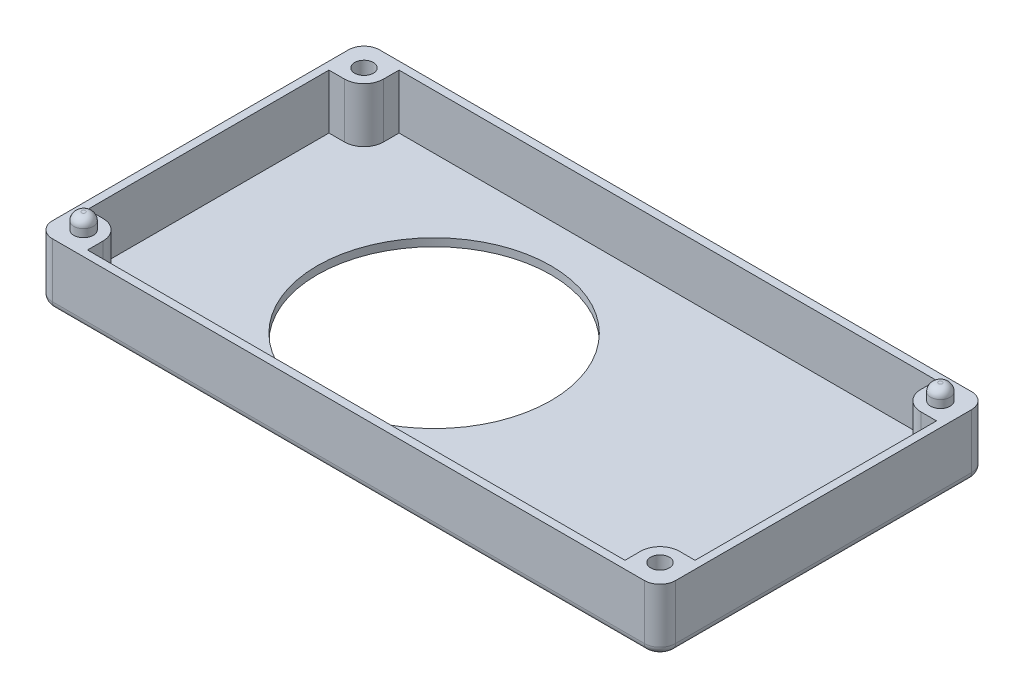
SolidWorks part; units mm, degrees
ref_plane "Front Plane" through (0, 0, 0) normal (0, 0, 1) x (1, 0, 0)
ref_plane "Top Plane" through (0, 0, 0) normal (0, 1, 0) x (1, 0, 0)
ref_plane "Right Plane" through (0, 0, 0) normal (1, 0, 0) x (0, 0, -1)
sketch "Sketch1" plane through (0, 0, 0) normal (0, 1, 0) x (1, 0, 0)
  line L1 (-40, -21) -> (40, -21)
  line L2 (-40, -21) -> (-40, 21)
  line L3 (-40, 21) -> (40, 21)
  line L4 (40, -21) -> (40, 21)
  line L5 (-40, -21) -> (40, 21) construction
  line L6 (-40, 21) -> (40, -21) construction
  point P0 (0, 0)
  dimension "D1" = 42
  dimension "D2" = 80
extrude "Boss-Extrude1" add sketch "Sketch1" along normal blind 8
sketch "Sketch2" plane through (0, 8, 0) normal (0, 1, 0) x (1, 0, 0)
  line L0 (40, -21) -> (40, 21) construction
  line L1 (-39, -20) -> (39, -20)
  line L2 (-39, -20) -> (-39, 20)
  line L3 (-39, 20) -> (39, 20)
  line L4 (39, -20) -> (39, 20)
  line L5 (-39, -20) -> (39, 20) construction
  line L6 (-39, 20) -> (39, -20) construction
  line L7 (40, 21) -> (-40, 21) construction
  point P0 (0, 0)
  dimension "D1" = 1
  dimension "D2" = 1
extrude "Cut-Extrude1" cut sketch "Sketch2" against normal offset from surface (7 mm away) 1 up to face at (0, 0, 0)
fillet "Fillet1" radius 2 8 edges at (40, 4, -21) (40, 4, 21) (-40, 4, 21) (-40, 4, -21) (39, 4.5, 20) (-39, 4.5, 20) (39, 4.5, -20) (-39, 4.5, -20)
sketch "Sketch3" plane through (0, 8, 0) normal (0, 1, 0) x (1, 0, 0)
  line L0 (-34.5, 18) -> (-34.5, 20)
  line L1 (37, 20) -> (-37, 20) construction
  line L2 (-37, 15.5) -> (-39, 15.5)
  line L3 (-39, 18) -> (-39, -18) construction
  line L4 (-39, 18) -> (-39, -18) construction
  line L5 (-39, 18) -> (-39, 15.5)
  line L6 (-34.5, 20) -> (-37, 20)
  arc A0 (-37, 15.5) -> (-34.5, 18) centre (-37, 18) ccw
  arc A1 (-37, 20) -> (-39, 18) centre (-37, 18) ccw construction
  arc A2 (-37, 20) -> (-39, 18) centre (-37, 18) ccw
  dimension "D1" = 5
extrude "Boss-Extrude2" add sketch "Sketch3" against normal up to next
mirror "Mirror1" about plane through (0, 0, 0) normal (0, 0, 1) of "Boss-Extrude2" second plane through (0, 0, 0) second plane normal (1, 0, 0)
hole_wizard "M2 Clearance Hole2" positions "3DSketch2" profile "Sketch8" hole size "M2" standard "ANSI Metric" end condition through all
sketch3d "3DSketch2"
  line L0 (-37, 1, -18) -> (-37, 8, -18) construction
  line L2 (37, 1, 18) -> (37, 8, 18) construction
  point P0 (-37, 8, -18)
  point P10 (37, 8, 18)
sketch "Sketch8" plane through (-37, 8, -18) normal (1, 0, 0) x (0, 0, 1)
  line L0 (0, 0) -> (0, 8)
  line L1 (0, 8) -> (1.2, 8)
  line L2 (1.2, 8) -> (1.2, 0)
  line L5 (1.2, 0) -> (0, 0)
  line L11 (0, -6.35) -> (0, 107.95) construction
  dimension "Thru Hole Dia." = 2.4
  dimension "Thru Hole Depth" = 8
sketch "Sketch9" plane through (0, 0, 0) normal (0, -1, 0) x (1, 0, 0)
  circle A0 centre (-37, -18) radius 2
  circle A1 centre (37, 18) radius 2
  dimension "D1" = 4
extrude "Cut-Extrude2" cut sketch "Sketch9" against normal blind 2.5
sketch "Sketch11" plane through (0, 8, 0) normal (0, 1, 0) x (1, 0, 0)
  circle A0 centre (-37, -18) radius 1.25
  circle A1 centre (37, 18) radius 1.25
  dimension "D1" = 2.5
extrude "Boss-Extrude3" add sketch "Sketch11" along normal blind 2
fillet "Fillet2" radius 1 2 edges at (37, 10, -16.75) (-37, 10, 19.25)
fillet "Fillet3" radius 1 8 edges at (-39.4142, 0, -20.4142) (0, 0, -21) (39.4142, 0, -20.4142) (40, 0, 0) (39.4142, 0, 20.4142) (0, 0, 21) (-39.4142, 0, 20.4142) (-40, 0, 0)
sketch "Sketch12" plane through (0, 0, 0) normal (0, -1, 0) x (1, 0, 0)
  line L0 (55, 0) -> (-55, 0) construction
  line L1 (-40, -19) -> (-40, 19) construction
  circle A0 centre (-10, 0) radius 15
  dimension "D1" = 30
  dimension "D2" = 30
extrude "Cut-Extrude3" cut sketch "Sketch12" against normal up to next
